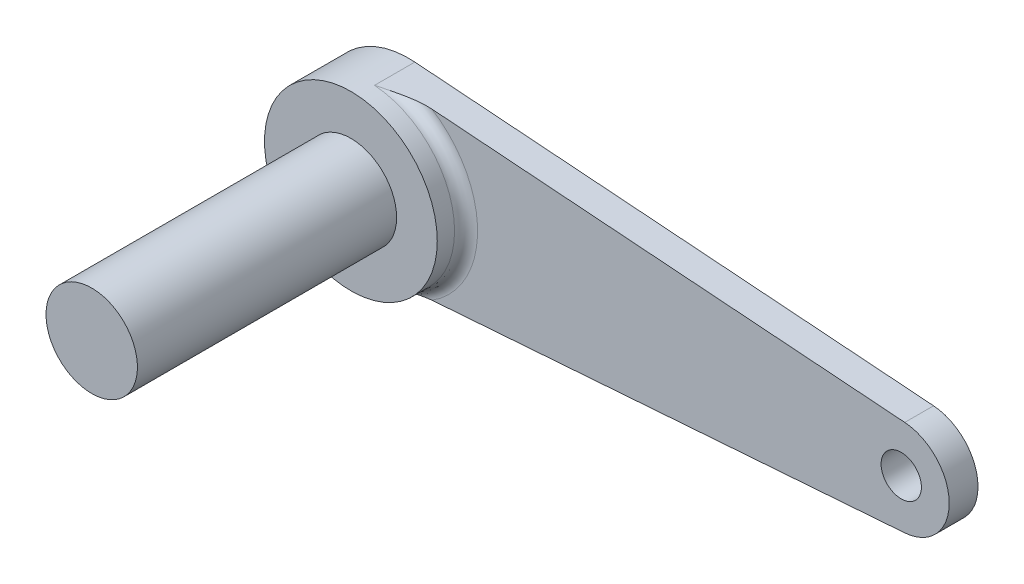
SolidWorks part; units mm, degrees
ref_plane "Front Plane" through (0, 0, 0) normal (0, 0, 1) x (1, 0, 0)
ref_plane "Top Plane" through (0, 0, 0) normal (0, 1, 0) x (1, 0, 0)
ref_plane "Right Plane" through (0, 0, 0) normal (1, 0, 0) x (0, 0, -1)
sketch "Sketch1" plane through (0, 0, 0) normal (0, 0, 1) x (1, 0, 0)
  line L0 (0, 0) -> (115.0046, 0) construction
  line L1 (115.7839, 10.5486) -> (1.4035, 18.9982)
  line L2 (115.7839, -10.5486) -> (1.4035, -18.9982)
  arc A0 (1.4035, 18.9982) -> (1.4035, -18.9982) centre (0, 0) ccw
  arc A1 (115.7839, -10.5486) -> (115.7839, 10.5486) centre (115.0046, 0) ccw
  dimension "D1" = 38.1
extrude "Extrude1" add sketch "Sketch1" against normal blind 6.35
sketch "Sketch2" plane through (0, 0, 0) normal (0, 0, 1) x (1, 0, 0)
  circle A0 centre (0, 0) radius 19.05
extrude "Extrude2" add sketch "Sketch2" along normal blind 6.35
ref_plane "Plane1" through (0, 0, 6.35) normal (0, 0, 1) x (1, 0, 0)
sketch "Sketch3" plane through (0, 0, 6.35) normal (0, 0, 1) x (1, 0, 0)
  circle A0 centre (0, 0) radius 10.08
extrude "Extrude3" cut sketch "Sketch3" against normal through all
sketch "Sketch4" plane through (0, 0, 0) normal (0, 0, 1) x (1, 0, 0)
  circle A0 centre (115.0046, 0) radius 4.4453
extrude "Extrude4" cut sketch "Sketch4" against normal blind 6.35
fillet "Fillet1" radius 2.54 1 edges
ref_plane "Plane2" through (0, 0, -6.35) normal (0, 0, -1) x (-1, 0, 0)
sketch "Sketch5" plane through (0, 0, -6.35) normal (0, 0, -1) x (-1, 0, 0)
  circle A0 centre (0, 0) radius 10.08 construction
  circle A1 centre (0, 0) radius 10.08
extrude "Extrude5" add sketch "Sketch5" against normal blind 69.85
